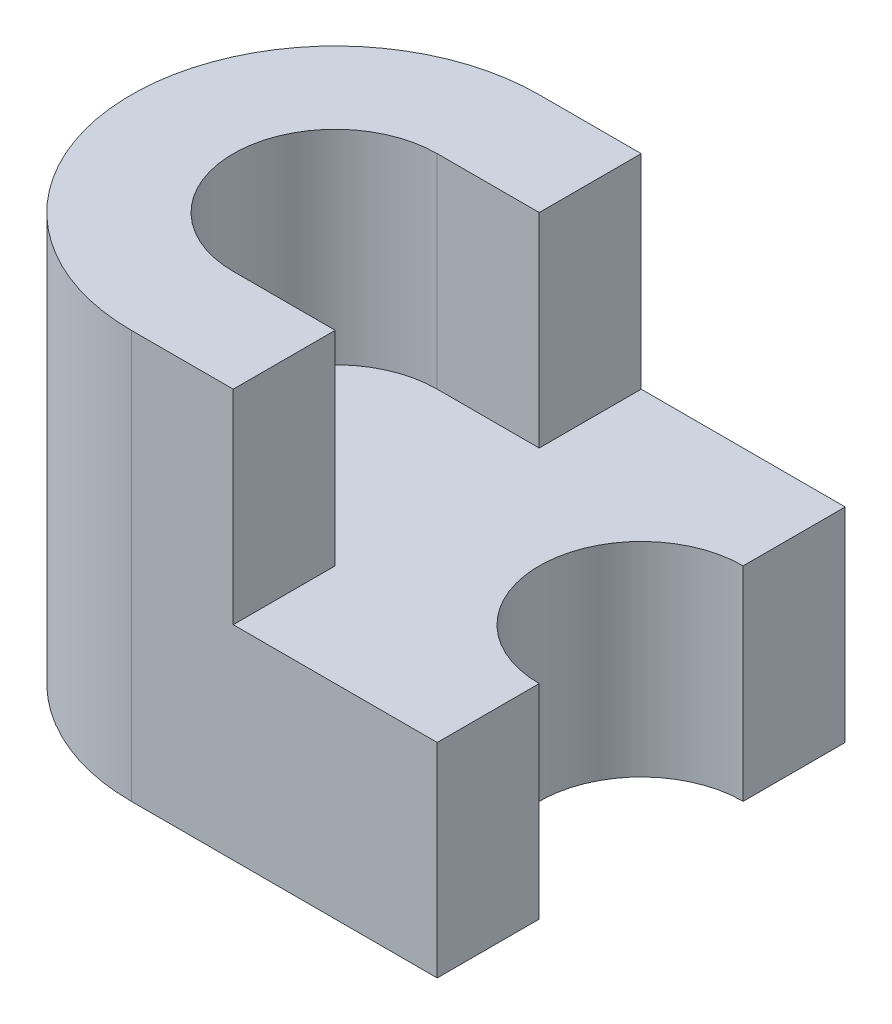
SolidWorks part; units mm, degrees
ref_plane "前基準面" through (0, 0, 0) normal (0, 0, 1) x (1, 0, 0)
ref_plane "上基準面" through (0, 0, 0) normal (0, 1, 0) x (1, 0, 0)
ref_plane "右基準面" through (0, 0, 0) normal (1, 0, 0) x (0, 0, -1)
sketch "草圖1" plane through (0, 0, 0) normal (0, 1, 0) x (1, 0, 0)
  line L0 (0, 0) -> (15, 0) construction
  line L1 (15, 0) -> (15, -3.7562) construction
  line L2 (0, 0) -> (0, 11.426) construction
  line L3 (5, 10) -> (5, 5)
  line L4 (0, 10) -> (15, 10)
  line L5 (15, 10) -> (15, 5)
  line L6 (15, -5) -> (15, -10)
  line L7 (15, -10) -> (0, -10)
  line L8 (0, 5) -> (5, 5)
  line L9 (0, -5) -> (5, -5)
  line L10 (5, -10) -> (5, -5)
  arc A0 (0, 10) -> (0, -10) centre (0, 0) ccw
  arc A1 (0, 5) -> (0, -5) centre (0, 0) ccw
  arc A2 (15, 5) -> (15, -5) centre (15, 0) ccw
  dimension "D1" = 15
  dimension "D2" = 10
  dimension "D3" = 20
  dimension "D4" = 10
  dimension "D5" = 5
extrude "填料-伸長1" add sketch "草圖1" along normal blind 10 contours A2 L5 L4 L3 L8 A1 L9 L10 L7 L6 | A1 L8 L3 L4 A0 L7 L10 L9 region at (6.1438, 0, 0) region at (4.75, 0, -7.5)
extrude "填料-伸長2" add sketch "草圖1<3>" along normal blind 20 contours A1 L8 L3 L4 A0 L7 L10 L9 region at (4.75, 0, -7.5)
sketch "草圖1<3>" plane through (0, 0, 0) normal (0, 1, 0) x (1, 0, 0) same geometry as "草圖1"
